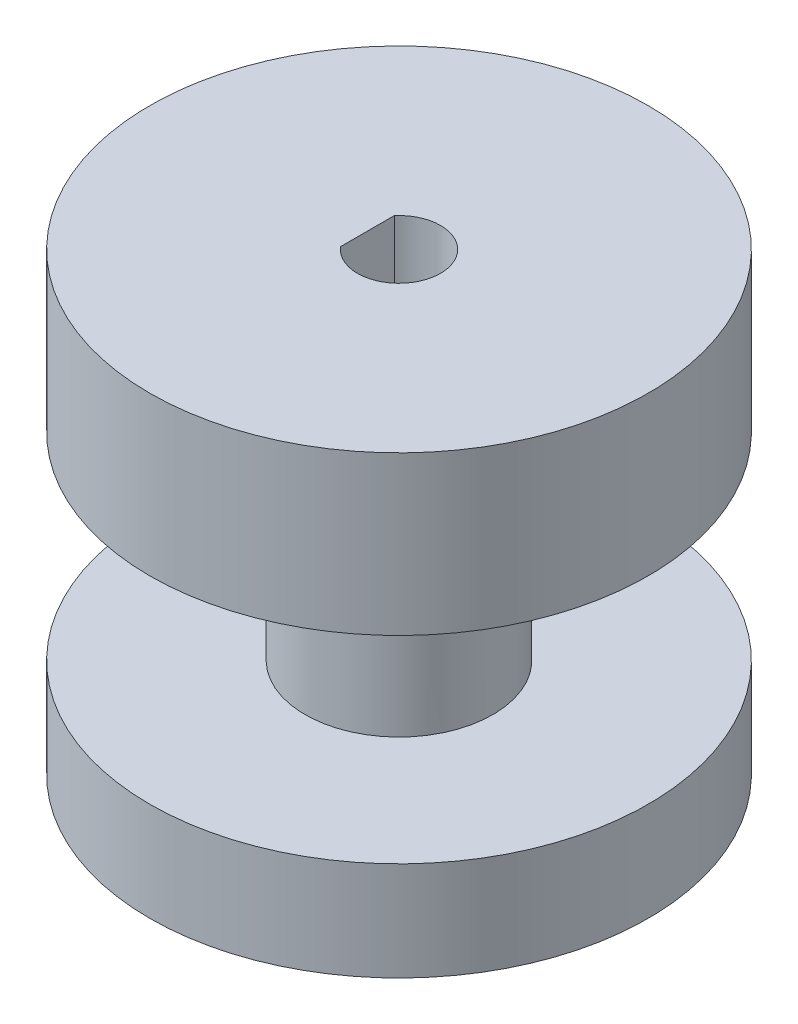
SolidWorks part; units mm, degrees
ref_plane "Front Plane" through (0, 0, 0) normal (0, 0, 1) x (1, 0, 0)
ref_plane "Top Plane" through (0, 0, 0) normal (0, 1, 0) x (1, 0, 0)
ref_plane "Right Plane" through (0, 0, 0) normal (1, 0, 0) x (0, 0, -1)
sketch "Sketch1" plane through (0, 0, 0) normal (0, 1, 0) x (1, 0, 0)
  circle A0 centre (0, 0) radius 4.75
extrude "Boss-Extrude1" add sketch "Sketch1" along normal blind 10 contours A0
sketch "Sketch2" plane through (0, 0, 0) normal (0, -1, 0) x (1, 0, 0)
  circle A0 centre (0, 0) radius 12.6
sketch "Sketch3" plane through (0, 10, 0) normal (0, 1, 0) x (1, 0, 0)
  circle A0 centre (0, 0) radius 12.6
extrude "Boss-Extrude2" add sketch "Sketch2" along normal blind 5 contours A0
sketch "Sketch4" plane through (0, 10, 0) normal (0, 1, 0) x (1, 0, 0)
  circle A0 centre (0, 0) radius 1.5
extrude "Cut-Extrude4" [suppressed] cut sketch "Sketch4" against normal up to surface (18 mm away) contours A0 up to face at (0, -5, -12.6)
extrude "Boss-Extrude4" add sketch "Sketch3" along normal blind 8 contours A0
sketch "Sketch5" plane through (0, 18, 0) normal (0, 1, 0) x (1, 0, 0)
  circle A0 centre (0, 0) radius 2.1
extrude "Cut-Extrude5" cut sketch "Sketch5" against normal up to surface (23 mm away) contours A0 up to face at (0, -5, -12.6)
sketch "Sketch6" plane through (0, 18, 0) normal (0, 1, 0) x (1, 0, 0)
  line L1 (-2.6, 2.4469) -> (-1.6, 2.4469)
  line L2 (-2.6, 2.4469) -> (-2.6, -2.4469)
  line L3 (-2.6, -2.4469) -> (-1.6, -2.4469)
  line L4 (-1.6, 2.4469) -> (-1.6, -2.4469)
  line L5 (-2.6, 2.4469) -> (-1.6, -2.4469) construction
  line L6 (-2.6, -2.4469) -> (-1.6, 2.4469) construction
  point P0 (-2.1, 0)
  dimension "D1" = 2.1
  dimension "D2" = 1
extrude "Boss-Extrude5" add sketch "Sketch6" against normal up to surface (8 mm away) contours L4 L3 L2 L1 up to face at (0, 10, 12.6)
hole_wizard "M2 Clearance Hole2" positions "3DSketch6" profile "Sketch12" hole size "M2" standard "ANSI Metric"
sketch3d "3DSketch6"
  point P0 (1.8035, 4.7631, -4.3943)
  dimension "D1" = 6.7268
sketch "Sketch12" plane through (1.8035, 4.7631, -4.3943) normal (0, 1, 0) x (-0.9251, 0, -0.3797)
  line L0 (0, 0) -> (0, 30.661)
  line L1 (0, 30.661) -> (1.2, 29.94)
  line L2 (1.2, 29.94) -> (1.2, 0)
  line L5 (1.2, 0) -> (0, 0)
  line L10 (0, 30.661) -> (-1.2, 29.94) construction
  line L11 (0, -6.35) -> (0, 107.95) construction
  dimension "Hole Dia." = 2.4
  dimension "Hole Depth" = 29.94
  dimension "Drill Angle" = 118
ref_plane "Plane1" through (-12.6, 0, 0) normal (-1, 0, 0) x (0, 0, 1)
hole_wizard "Tap Drill for M2x0.4 Tap1" positions "Sketch15" profile "Sketch14" hole size "M2x0.4" standard "ANSI Metric"
sketch "Sketch15" plane through (-12.6, 0, 0) normal (-1, 0, 0) x (0, 0, 1)
  line L0 (12.6, 18) -> (-12.6, 18) construction
  point P0 (0, 14)
  point P2 (0, 14)
  dimension "D1" = 4
sketch "Sketch14" plane through (-12.6, 14, 0) normal (0, 1, 0) x (0, 0, 1)
  line L0 (0, 0) -> (0, 16.4807)
  line L1 (0, 16.4807) -> (0.8, 16)
  line L2 (0.8, 16) -> (0.8, 0)
  line L5 (0.8, 0) -> (0, 0)
  line L10 (0, 16.4807) -> (-0.8, 16) construction
  line L11 (0, -6.35) -> (0, 107.95) construction
  dimension "Hole Dia." = 1.6
  dimension "Hole Depth" = 16
  dimension "Drill Angle" = 118
